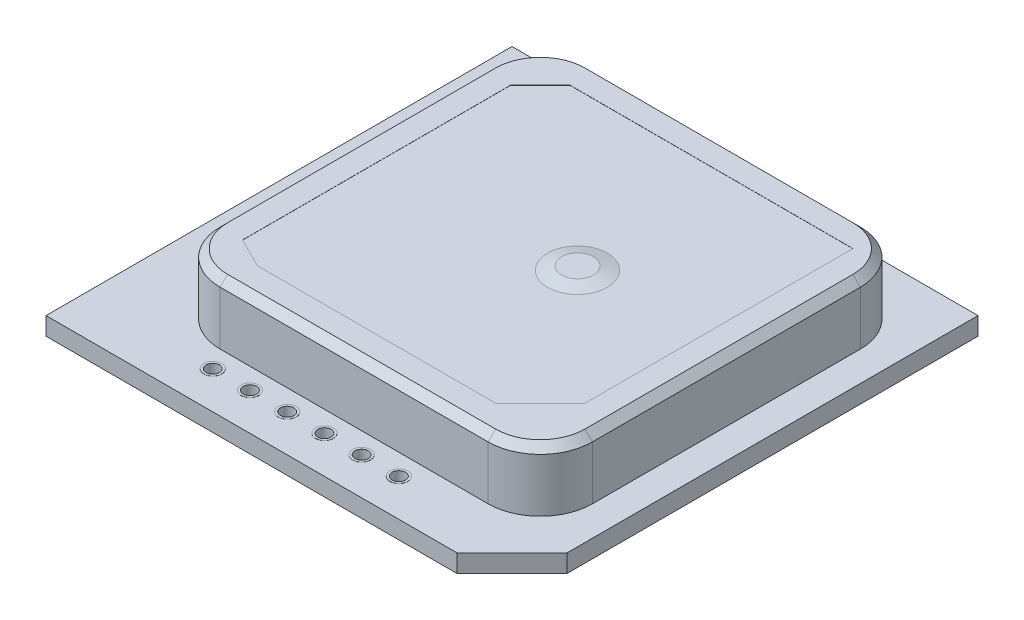
SolidWorks part; units mm, degrees
material "Сплав АМг6 ГОСТ 4784-97"
ref_plane "Спереди" through (0, 0, 0) normal (0, 0, 1) x (1, 0, 0)
ref_plane "Сверху" through (0, 0, 0) normal (0, 1, 0) x (1, 0, 0)
ref_plane "Справа" through (0, 0, 0) normal (1, 0, 0) x (0, 0, -1)
sketch "Эскиз1" plane through (0, 0, 0) normal (0, 1, 0) x (1, 0, 0)
  line L0 (11.95, -15.65) -> (15.65, -11.95)
  line L1 (-15.65, 15.65) -> (15.65, 15.65)
  line L2 (-15.65, 15.65) -> (-15.65, -15.65)
  line L3 (-15.65, -15.65) -> (11.95, -15.65)
  line L4 (15.65, 15.65) -> (15.65, -11.95)
  line L5 (-15.65, 15.65) -> (15.65, -15.65) construction
  line L6 (-15.65, -15.65) -> (15.65, 15.65) construction
  point P0 (0, 0)
  dimension "D1" = 31.3
extrude "Бобышка-Вытянуть1" add sketch "Эскиз1" along normal blind 1.2
sketch "Эскиз2" plane through (0, 1.2, 0) normal (0, 1, 0) x (1, 0, 0)
  line L0 (15.65, -11.95) -> (15.65, 15.65) construction
  line L1 (-7.85, 13.25) -> (10.15, 13.25)
  line L2 (-11.35, 9.75) -> (-11.35, -8.25)
  line L3 (-7.85, -11.75) -> (10.15, -11.75)
  line L4 (13.65, 9.75) -> (13.65, -8.25)
  line L5 (15.65, 15.65) -> (-15.65, 15.65) construction
  arc A0 (-11.35, -8.25) -> (-7.85, -11.75) centre (-7.85, -8.25) ccw
  arc A1 (10.15, -11.75) -> (13.65, -8.25) centre (10.15, -8.25) ccw
  arc A2 (10.15, 13.25) -> (13.65, 9.75) centre (10.15, 9.75) cw
  arc A3 (-7.85, 13.25) -> (-11.35, 9.75) centre (-7.85, 9.75) ccw
  point P4 (-12.6661, 12.9531)
  point P11 (-11.35, -11.75)
  point P18 (-11.35, 13.25)
  dimension "D4" = 3.5
  dimension "D1" = 25
  dimension "D2" = 2
  dimension "D3" = 2.4
extrude "Бобышка-Вытянуть2" add sketch "Эскиз2" along normal blind 4.1 separate body
chamfer "Фаска1" distance 0.5 angle 45 8 edges at (-11.35, 5.3, -0.75) (-10.3249, 5.3, 10.7249) (-10.3249, 5.3, -12.2249) (1.15, 5.3, 11.75) (1.15, 5.3, -13.25) (12.6249, 5.3, 10.7249) (12.6249, 5.3, -12.2249) (13.65, 5.3, -0.75)
sketch "Эскиз3" plane through (0, 5.3, 0) normal (0, 1, 0) x (1, 0, 0)
  line L0 (-7.85, 13.25) -> (10.15, 13.25) construction
  line L1 (-7.35, 11.25) -> (11.65, 11.25)
  line L2 (-9.35, 9.25) -> (-9.35, -8.75)
  line L3 (-7.35, -9.75) -> (8.65, -9.75)
  line L4 (11.65, 11.25) -> (11.65, -6.75)
  line L5 (13.65, 9.75) -> (13.65, -8.25) construction
  line L6 (-9.35, 9.25) -> (-7.35, 11.25)
  line L7 (8.65, -9.75) -> (11.65, -6.75)
  line L8 (-9.35, -8.75) -> (-7.35, -9.75)
  point P0 (-9.35, 11.25)
  point P1 (11.65, -9.75)
  point P2 (-9.35, -9.75)
  dimension "D1" = 21
  dimension "D2" = 2
  dimension "D3" = 2
  dimension "D4" = 1
  dimension "D5" = 2
  dimension "D8" = 21
extrude "Вырез-Вытянуть1" cut sketch "Эскиз3" against normal blind 0.01
sketch "Эскиз4" plane through (0, 5.29, 0) normal (0, 1, 0) x (1, 0, 0)
  line L0 (13.65, 9.75) -> (13.65, -8.25) construction
  line L1 (-7.85, 13.25) -> (10.15, 13.25) construction
  circle A0 centre (3.65, 0.75) radius 2
  dimension "D1" = 4
  dimension "D2" = 10
  dimension "D3" = 12.5
extrude "Бобышка-Вытянуть3" add sketch "Эскиз4" along normal blind 0.25 draft 75
sketch "Эскиз5" plane through (0, 1.2, 0) normal (0, 1, 0) x (1, 0, 0)
  line L0 (-15.65, 15.65) -> (-15.65, -15.65) construction
  line L1 (-14.15, 12.65) -> (-13.35, 12.65)
  line L2 (-14.15, 12.65) -> (-14.15, 10.95)
  line L3 (-14.15, 10.95) -> (-13.35, 10.95)
  line L4 (-13.35, 12.65) -> (-13.35, 10.95)
  line L5 (15.65, 15.65) -> (-15.65, 15.65) construction
  dimension "D1" = 1.7
  dimension "D2" = 0.8
  dimension "D3" = 1.5
  dimension "D4" = 3
extrude "Бобышка-Вытянуть4" add sketch "Эскиз5" along normal blind 0.5
hole_wizard "Диаметр отверстия Ø0.9 (0.9)1" positions "Эскиз6" profile "Эскиз7" hole size "Ø0.9" standard "GOST" end condition through all
sketch "Эскиз6" plane through (0, 1.2, 0) normal (0, 1, 0) x (1, 0, 0)
  line L0 (-15.65, -15.65) -> (11.95, -15.65) construction
  line L1 (-15.65, 15.65) -> (-15.65, -15.65) construction
  point P0 (-6.95, -13.15)
  dimension "D1" = 2.5
  dimension "D2" = 8.7
sketch "Эскиз7" plane through (-6.95, 1.2, 13.15) normal (1, 0, 0) x (0, 0, 1)
  line L0 (0, 0) -> (0, 1.21)
  line L1 (0, 1.21) -> (0.45, 1.21)
  line L2 (0.45, 1.21) -> (0.45, 0)
  line L5 (0.45, 0) -> (0, 0)
  line L11 (0, -6.35) -> (0, 107.95) construction
  dimension "Диаметр сквозного отверстия" = 0.9
  dimension "Глубина сквозного отверстия" = 1.21
sketch "Эскиз8" plane through (0, 1.2, 0) normal (0, 1, 0) x (1, 0, 0)
  circle A0 centre (-6.95, -13.15) radius 0.45 construction
  circle A1 centre (-6.95, -13.15) radius 0.45
  circle A2 centre (-6.95, -13.15) radius 0.6
extrude "Бобышка-Вытянуть5" add sketch "Эскиз8" along normal blind 0.01 and the other way blind 1.21
pattern_linear "Линейный массив1" count 6 spacing 2.5 along (1, 0, 0) of "Диаметр отверстия Ø0.9 (0.9)1", "Бобышка-Вытянуть5"
sketch "Эскиз9" plane through (0, 0, 0) normal (0, -1, 0) x (1, 0, 0)
  line L0 (13.8, 13.8) -> (12.0322, 12.0322) construction
  line L1 (11.95, 15.65) -> (15.65, 11.95) construction
  line L2 (12.0322, 12.0322) -> (9.9109, 9.9109) construction
  line L3 (9.9109, 9.9109) -> (11.608, 15.2849)
  line L4 (11.608, 15.2849) -> (12.0322, 12.0322)
  line L5 (12.0322, 12.0322) -> (15.2849, 11.608)
  line L6 (15.2849, 11.608) -> (9.9109, 9.9109)
  line L7 (11.608, 15.2849) -> (15.2849, 11.608) construction
  dimension "D1" = 5.2
  dimension "D2" = 0.5
  dimension "D3" = 2.5
  dimension "D4" = 5.5
extrude "Вырез-Вытянуть2" cut sketch "Эскиз9" against normal blind 0.01
sketch "Эскиз10" plane through (0, 0, 0) normal (0, -1, 0) x (1, 0, 0)
  line L0 (-15.65, -15.65) -> (-15.65, 15.65) construction
  line L1 (-12.65, 2.45) -> (-0.35, 2.45)
  line L2 (-12.65, 2.45) -> (-12.65, -13.65)
  line L3 (-12.65, -13.65) -> (-0.35, -13.65)
  line L4 (-0.35, 2.45) -> (-0.35, -13.65)
  line L5 (15.65, -15.65) -> (-15.65, -15.65) construction
  dimension "D1" = 16.1
  dimension "D2" = 12.3
  dimension "D3" = 3
  dimension "D4" = 2
extrude "Бобышка-Вытянуть6" add sketch "Эскиз10" along normal blind 2.9
sketch "Эскиз11" plane through (0, -2.9, 0) normal (0, -1, 0) x (1, 0, 0)
  line L0 (-10.6712, 1.6022) -> (-10.6712, -12.649) construction
  text T0 "UBlox\r\nNEO-M8N-0-01\r\n41300585930\r\n1521\r\n0800  34" font "Arial" height 0.8
extrude "Вырез-Вытянуть3" cut sketch "Эскиз11" against normal blind 0.01
sketch "Эскиз12" plane through (0, 0, 0) normal (0, -1, 0) x (1, 0, 0)
  line L0 (6.5004, -7.15) -> (5.95, -7.15)
  line L1 (5.95, -7.15) -> (5.95, -9.15)
  line L2 (5.95, -9.15) -> (6.5004, -9.15)
  line L3 (15.65, 11.95) -> (15.65, -15.65) construction
  line L4 (15.65, -15.65) -> (-15.65, -15.65) construction
  arc A0 (6.5004, -9.15) -> (6.5004, -7.15) centre (9.75, -8.15) ccw
  point P1 (0, 0)
  point P8 (6.5004, -9.0376)
  dimension "D1" = 6.8
  dimension "D2" = 7.2
  dimension "D3" = 2
  dimension "D4" = 2.5
  dimension "D5" = 7.5
extrude "Бобышка-Вытянуть7" add sketch "Эскиз12" along normal blind 2
sketch "Эскиз13" plane through (0, 0, 0) normal (0, -1, 0) x (1, 0, 0)
  line L0 (8.9918, 9.6035) -> (10.5562, 7.5426)
  line L1 (2.0773, -12.3729) -> (3.737, -12.3729)
  line L2 (2.0773, -12.3729) -> (2.0773, -13.0368)
  line L3 (2.0773, -13.0368) -> (3.737, -13.0368)
  line L4 (3.737, -12.3729) -> (3.737, -13.0368)
  line L5 (12.5334, -0.7135) -> (13.1143, -0.7135)
  line L6 (12.5334, -0.7135) -> (12.5334, -2.2902)
  line L7 (12.5334, -2.2902) -> (13.1143, -2.2902)
  line L8 (13.1143, -0.7135) -> (13.1143, -2.2902)
  line L9 (12.243, 3.5602) -> (13.4878, 3.5602)
  line L10 (12.243, 3.5602) -> (12.243, 1.3611)
  line L11 (12.243, 1.3611) -> (13.4878, 1.3611)
  line L12 (13.4878, 3.5602) -> (13.4878, 1.3611)
  line L13 (11.2472, 8.3734) -> (11.7036, 8.3734)
  line L14 (11.2472, 8.3734) -> (11.2472, 7.0871)
  line L15 (11.2472, 7.0871) -> (11.7036, 7.0871)
  line L16 (11.7036, 8.3734) -> (11.7036, 7.0871)
  line L17 (8.9918, 9.6035) -> (7.0029, 8.0938)
  line L18 (10.5562, 7.5426) -> (8.5672, 6.0328)
  line L19 (7.0029, 8.0938) -> (8.5672, 6.0328)
  line L21 (8.3742, 10.6072) -> (9.5709, 10.6072)
  line L22 (8.3742, 10.6072) -> (8.3742, 10.1054)
  line L23 (8.3742, 10.1054) -> (9.5709, 10.1054)
  line L24 (9.5709, 10.6072) -> (9.5709, 10.1054)
  line L25 (6.1353, 8.7157) -> (6.6564, 8.7157)
  line L26 (6.1353, 8.7157) -> (6.1353, 7.2874)
  line L27 (6.1353, 7.2874) -> (6.6564, 7.2874)
  line L28 (6.6564, 8.7157) -> (6.6564, 7.2874)
  line L29 (0.1684, 10.6072) -> (0.8, 10.6072)
  line L30 (0.1684, 10.6072) -> (0.1684, 9.2542)
  line L31 (0.1684, 9.2542) -> (0.8, 9.2542)
  line L32 (0.8, 10.6072) -> (0.8, 9.2542)
  line L33 (-2.358, 10.6072) -> (-1.6715, 10.6072)
  line L34 (-2.358, 10.6072) -> (-2.358, 9.2542)
  line L35 (-2.358, 9.2542) -> (-1.6715, 9.2542)
  line L36 (-1.6715, 10.6072) -> (-1.6715, 9.2542)
  line L37 (-8.9213, 10.6072) -> (-8.3171, 10.6072)
  line L38 (-8.9213, 10.6072) -> (-8.9213, 9.2542)
  line L39 (-8.9213, 9.2542) -> (-8.3171, 9.2542)
  line L40 (-8.3171, 10.6072) -> (-8.3171, 9.2542)
  line L41 (-12.6011, 12.577) -> (-11.1182, 12.577)
  line L42 (-12.6011, 12.577) -> (-12.6011, 11.8081)
  line L43 (-12.6011, 11.8081) -> (-11.1182, 11.8081)
  line L44 (-11.1182, 12.577) -> (-11.1182, 11.8081)
  line L45 (-12.6011, 7.5426) -> (-10.871, 7.5426)
  line L46 (-12.6011, 7.5426) -> (-12.6011, 6.6454)
  line L47 (-12.6011, 6.6454) -> (-10.871, 6.6454)
  line L48 (-10.871, 7.5426) -> (-10.871, 6.6454)
  line L49 (-11.4752, 10.9293) -> (-10.0472, 10.9293)
  line L50 (-11.4752, 10.9293) -> (-11.4752, 8.3734)
  line L51 (-11.4752, 8.3734) -> (-10.0472, 8.3734)
  line L52 (-10.0472, 10.9293) -> (-10.0472, 8.3734)
extrude "Бобышка-Вытянуть8" add sketch "Эскиз13" along normal blind 1.1
sketch "Эскиз14" plane through (0, 0, 0) normal (0, -1, 0) x (1, 0, 0)
  text T0 "GND         VCC        TXD         RXD          SCL         SDA" font "Arial" height 0.4
extrude "Вырез-Вытянуть4" cut sketch "Эскиз14" against normal blind 0.01
